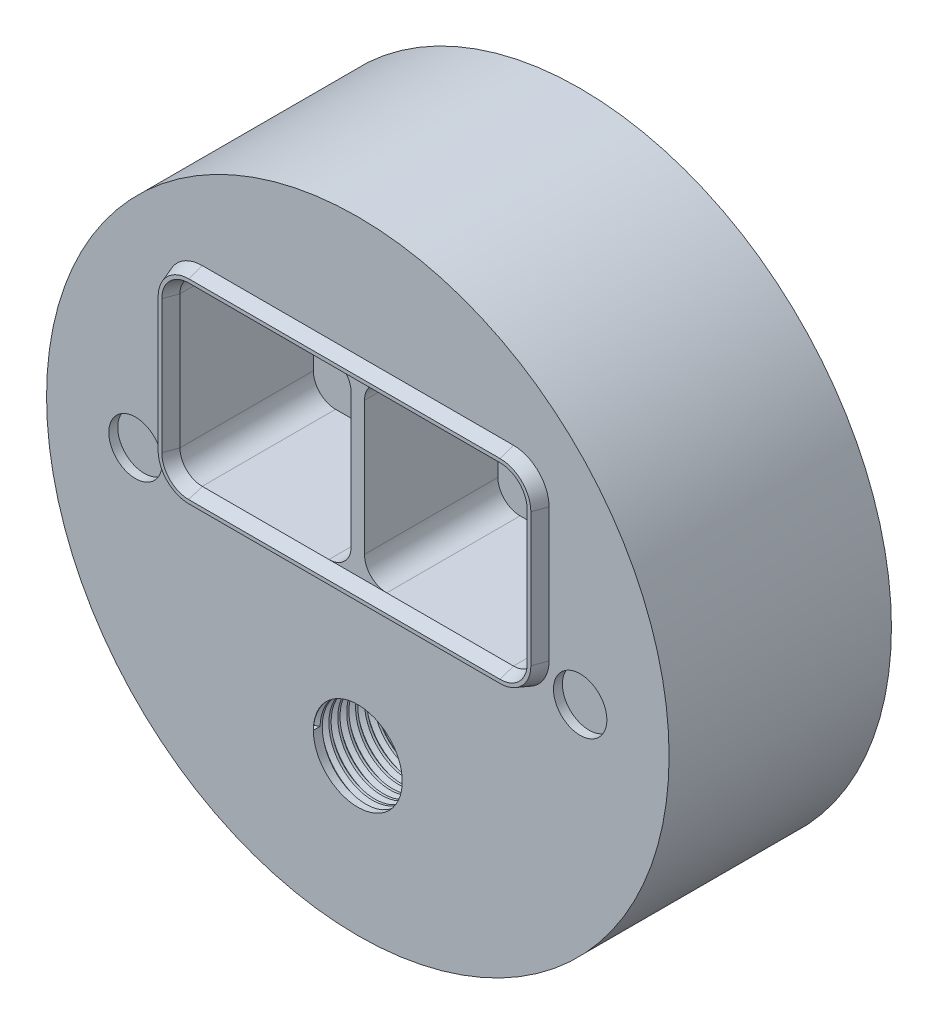
SolidWorks part; units mm, degrees
ref_plane "Front Plane" through (0, 0, 0) normal (0, 0, 1) x (1, 0, 0)
ref_plane "Top Plane" through (0, 0, 0) normal (0, 1, 0) x (1, 0, 0)
ref_plane "Right Plane" through (0, 0, 0) normal (1, 0, 0) x (0, 0, -1)
sketch "Sketch1" plane through (0, 0, 0) normal (0, 0, 1) x (1, 0, 0)
  line L0 (0, 0) -> (0, -35) construction
  line L1 (0, 0) -> (-25, 0) construction
  circle A0 centre (0, 0) radius 35
  circle A1 centre (0, -17.5) radius 5
  circle A2 centre (-25, 0) radius 3
  circle A3 centre (25, 0) radius 3
  dimension "D1" = 70
  dimension "D2" = 10
  dimension "D3" = 25
extrude "Boss-Extrude1" add sketch "Sketch1" along normal blind 25
thread "Thread1" pitch 1 start angle 0, offset 0, length 0, pitch 1, diameter 10
ref_plane "Plane1" through (-5, -17.5, 25) normal (0, -1, 0) x (-1, 0, 0)
sketch "Thread Profile1" plane through (-5, -17.5, 25) normal (0, -1, 0) x (-1, 0, 0)
  line L0 (0, 0) -> (0, 1) construction
  line L1 (0, 0) -> (0.5413, 0.3125)
  line L2 (0.5413, 0.3125) -> (0.5413, 0.4375)
  line L3 (0.5413, 0.4375) -> (0, 0.75)
  line L4 (0.5413, 0.375) -> (0, 0.375) construction
  line L11 (0, 0) -> (0, 0.75)
  point P2 (0, 0)
  dimension "Pitch" = 1
  dimension "Profile_Angle" = 60
  dimension "Profile_Land" = 0.125
  dimension "Profile_Height" = 0.5413
sketch "Sketch9" plane through (0, 0, 25) normal (0, 0, 1) x (1, 0, 0)
  circle A0 centre (-25, 0) radius 3
  circle A1 centre (25, 0) radius 3
extrude "Boss-Extrude2" add sketch "Sketch9" against normal up to surface (24 mm away) from offset 1 up to face at (22, 0, 0) offset against normal yes
sketch "Sketch10" plane through (0, 0, 25) normal (0, 0, 1) x (1, 0, 0)
  line L0 (0, 0) -> (0, 35) construction
  line L1 (-17.5, 20) -> (17.5, 20)
  line L2 (-20, 17.5) -> (-20, 2.5)
  line L3 (-17.5, 0) -> (17.5, 0)
  line L4 (20, 17.5) -> (20, 2.5)
  line L5 (0, 0) -> (0, 20) construction
  line L6 (-20, 10) -> (20, 10) construction
  circle A0 centre (0, 0) radius 35 construction
  arc A1 (-20, 2.5) -> (-17.5, 0) centre (-17.5, 2.5) ccw
  arc A2 (17.5, 0) -> (20, 2.5) centre (17.5, 2.5) ccw
  arc A3 (17.5, 20) -> (20, 17.5) centre (17.5, 17.5) cw
  arc A4 (-17.5, 20) -> (-20, 17.5) centre (-17.5, 17.5) ccw
  point P11 (-20, 0)
  point P16 (20, 20)
  point P19 (-20, 20)
  point P148 (0, 10)
  dimension "D4" = 2.5
  dimension "D1" = 10
  dimension "D2" = 20
  dimension "D3" = 40
extrude "Cut-Extrude1" cut sketch "Sketch10" against normal blind 15
sketch "Sketch11" plane through (0, 0, 10) normal (0, 0, 1) x (1, 0, 0)
  line L0 (0, 20) -> (0, 0) construction
  line L1 (17.5, 20) -> (-17.5, 20) construction
  line L2 (-17.5, 0) -> (17.5, 0) construction
  line L3 (0, 0) -> (0, 10) construction
  line L4 (0, 10) -> (20, 10) construction
  line L5 (20, 2.5) -> (20, 17.5) construction
  line L6 (-0.75, 17.5) -> (-0.75, 2.5)
  line L10 (0.75, 17.5) -> (0.75, 2.5)
  line L12 (-3.25, 20) -> (3.25, 20)
  line L13 (-3.25, 0) -> (3.25, 0)
  arc A1 (-3.25, 20) -> (-0.75, 17.5) centre (-3.25, 17.5) cw
  arc A2 (3.25, 20) -> (0.75, 17.5) centre (3.25, 17.5) ccw
  arc A3 (-3.25, 0) -> (-0.75, 2.5) centre (-3.25, 2.5) ccw
  arc A4 (3.25, 0) -> (0.75, 2.5) centre (3.25, 2.5) cw
  dimension "D1" = 2.5
  dimension ".15" = 1.5
extrude "Boss-Extrude3" add sketch "Sketch11" along normal up to surface (15 mm away) up to face at (0, 10, 25)
sketch "Sketch12" plane through (0, 0, 25) normal (0, 0, 1) x (1, 0, 0)
  line L0 (-3.25, 20) -> (-17.5, 20) construction
  line L1 (17.5, 20) -> (3.25, 20) construction
  line L2 (20, 2.5) -> (20, 17.5) construction
  line L3 (3.25, 0) -> (17.5, 0) construction
  line L4 (-17.5, 0) -> (-3.25, 0) construction
  line L5 (-20, 17.5) -> (-20, 2.5) construction
  line L6 (-3.25, 20) -> (-17.5, 20)
  line L7 (17.5, 20) -> (3.25, 20)
  line L8 (20, 2.5) -> (20, 17.5)
  line L9 (3.25, 0) -> (17.5, 0)
  line L10 (-17.5, 0) -> (-3.25, 0)
  line L11 (-20, 17.5) -> (-20, 2.5)
  line L12 (-3.25, 20) -> (3.25, 20)
  line L13 (-3.25, 0) -> (3.25, 0)
  line L14 (-3.25, -1.5) -> (3.25, -1.5)
  line L15 (3.25, -1.5) -> (17.5, -1.5)
  line L16 (21.5, 2.5) -> (21.5, 17.5)
  line L17 (17.5, 21.5) -> (3.25, 21.5)
  line L18 (-3.25, 21.5) -> (3.25, 21.5)
  line L19 (-3.25, 21.5) -> (-17.5, 21.5)
  line L20 (-21.5, 17.5) -> (-21.5, 2.5)
  line L21 (-17.5, -1.5) -> (-3.25, -1.5)
  arc A0 (20, 17.5) -> (17.5, 20) centre (17.5, 17.5) ccw construction
  arc A1 (17.5, 0) -> (20, 2.5) centre (17.5, 2.5) ccw construction
  arc A2 (-20, 2.5) -> (-17.5, 0) centre (-17.5, 2.5) ccw construction
  arc A3 (-17.5, 20) -> (-20, 17.5) centre (-17.5, 17.5) ccw construction
  arc A4 (20, 17.5) -> (17.5, 20) centre (17.5, 17.5) ccw
  arc A5 (17.5, 0) -> (20, 2.5) centre (17.5, 2.5) ccw
  arc A6 (-20, 2.5) -> (-17.5, 0) centre (-17.5, 2.5) ccw
  arc A7 (-17.5, 20) -> (-20, 17.5) centre (-17.5, 17.5) ccw
  arc A8 (17.5, -1.5) -> (21.5, 2.5) centre (17.5, 2.5) ccw
  arc A9 (21.5, 17.5) -> (17.5, 21.5) centre (17.5, 17.5) ccw
  arc A10 (-17.5, 21.5) -> (-21.5, 17.5) centre (-17.5, 17.5) ccw
  arc A11 (-21.5, 2.5) -> (-17.5, -1.5) centre (-17.5, 2.5) ccw
  dimension "D1" = 1.5
extrude "Boss-Extrude4" add sketch "Sketch12" along normal blind 1.5 draft 20
sketch "Sketch14" plane through (0, 0, 0) normal (0, 0, 1) x (1, 0, 0)
  line L0 (0, 0) -> (35, 0) construction
  line L1 (14.5611, 30) -> (14.0611, 30)
  line L2 (15.5611, 29) -> (15.5611, -29)
  line L3 (14.5611, -30) -> (14.0611, -30)
  line L4 (13.0611, 29) -> (13.0611, -29)
  line L5 (14.3111, -30) -> (14.3111, 30) construction
  line L6 (15.5611, 0) -> (13.0611, 0) construction
  circle A0 centre (0, 0) radius 35 construction
  arc A1 (15.5611, -29) -> (14.5611, -30) centre (14.5611, -29) cw
  arc A2 (14.0611, -30) -> (13.0611, -29) centre (14.0611, -29) cw
  arc A3 (14.5611, 30) -> (15.5611, 29) centre (14.5611, 29) cw
  arc A4 (14.0611, 30) -> (13.0611, 29) centre (14.0611, 29) ccw
  point P11 (15.5611, -30)
  point P16 (15.5611, 30)
  point P19 (13.0611, 30)
  point P1000 (14.3111, 0)
  dimension "D3" = 1
  dimension "D1" = 2.5
  dimension "D2" = 60
extrude "Cut-Extrude5" cut sketch "Sketch14" along normal blind 1 from surface at 0 starting at face at (35, 0, 0)
sketch "Sketch15" plane through (0, 0, 1) normal (0, 0, -1) x (-1, 0, 0)
  line L0 (-14.3111, -30) -> (-14.3111, 30) construction
  line L1 (-14.5611, -30) -> (-14.0611, -30) construction
  line L2 (-14.0611, 30) -> (-14.5611, 30) construction
  line L3 (-15.2253, 29.2498) -> (-15.2253, 28.8899)
  line L4 (-15.2253, 28.8899) -> (-14.3111, 28.2623)
  line L5 (-15.2253, 29.2498) -> (-14.3111, 28.6221)
  line L6 (-13.3968, 29.2498) -> (-13.3968, 28.8899)
  line L7 (-13.3968, 29.2498) -> (-14.3111, 28.6221)
  line L8 (-13.3968, 28.8899) -> (-14.3111, 28.2623)
  line L9 (-13.3968, 26.7498) -> (-13.3968, 26.3899)
  line L10 (-13.3968, 26.3899) -> (-14.3111, 25.7623)
  line L11 (-15.2253, 26.3899) -> (-14.3111, 25.7623)
  line L12 (-15.2253, 26.7498) -> (-15.2253, 26.3899)
  line L13 (-15.2253, 26.7498) -> (-14.3111, 26.1221)
  line L14 (-13.3968, 26.7498) -> (-14.3111, 26.1221)
  line L15 (-13.3968, 24.2498) -> (-13.3968, 23.8899)
  line L16 (-13.3968, 23.8899) -> (-14.3111, 23.2623)
  line L17 (-15.2253, 23.8899) -> (-14.3111, 23.2623)
  line L18 (-15.2253, 24.2498) -> (-15.2253, 23.8899)
  line L19 (-15.2253, 24.2498) -> (-14.3111, 23.6221)
  line L20 (-13.3968, 24.2498) -> (-14.3111, 23.6221)
  line L21 (-13.3968, 21.7498) -> (-13.3968, 21.3899)
  line L22 (-13.3968, 21.3899) -> (-14.3111, 20.7623)
  line L23 (-15.2253, 21.3899) -> (-14.3111, 20.7623)
  line L24 (-15.2253, 21.7498) -> (-15.2253, 21.3899)
  line L25 (-15.2253, 21.7498) -> (-14.3111, 21.1221)
  line L26 (-13.3968, 21.7498) -> (-14.3111, 21.1221)
  line L27 (-13.3968, 19.2498) -> (-13.3968, 18.8899)
  line L28 (-13.3968, 18.8899) -> (-14.3111, 18.2623)
  line L29 (-15.2253, 18.8899) -> (-14.3111, 18.2623)
  line L30 (-15.2253, 19.2498) -> (-15.2253, 18.8899)
  line L31 (-15.2253, 19.2498) -> (-14.3111, 18.6221)
  line L32 (-13.3968, 19.2498) -> (-14.3111, 18.6221)
  line L33 (-13.3968, 16.7498) -> (-13.3968, 16.3899)
  line L34 (-13.3968, 16.3899) -> (-14.3111, 15.7623)
  line L35 (-15.2253, 16.3899) -> (-14.3111, 15.7623)
  line L36 (-15.2253, 16.7498) -> (-15.2253, 16.3899)
  line L37 (-15.2253, 16.7498) -> (-14.3111, 16.1221)
  line L38 (-13.3968, 16.7498) -> (-14.3111, 16.1221)
  line L39 (-13.3968, 14.2498) -> (-13.3968, 13.8899)
  line L40 (-13.3968, 13.8899) -> (-14.3111, 13.2623)
  line L41 (-15.2253, 13.8899) -> (-14.3111, 13.2623)
  line L42 (-15.2253, 14.2498) -> (-15.2253, 13.8899)
  line L43 (-15.2253, 14.2498) -> (-14.3111, 13.6221)
  line L44 (-13.3968, 14.2498) -> (-14.3111, 13.6221)
  line L45 (-13.3968, 11.7498) -> (-13.3968, 11.3899)
  line L46 (-13.3968, 11.3899) -> (-14.3111, 10.7623)
  line L47 (-15.2253, 11.3899) -> (-14.3111, 10.7623)
  line L48 (-15.2253, 11.7498) -> (-15.2253, 11.3899)
  line L49 (-15.2253, 11.7498) -> (-14.3111, 11.1221)
  line L50 (-13.3968, 11.7498) -> (-14.3111, 11.1221)
  line L51 (-13.3968, 9.2498) -> (-13.3968, 8.8899)
  line L52 (-13.3968, 8.8899) -> (-14.3111, 8.2623)
  line L53 (-15.2253, 8.8899) -> (-14.3111, 8.2623)
  line L54 (-15.2253, 9.2498) -> (-15.2253, 8.8899)
  line L55 (-15.2253, 9.2498) -> (-14.3111, 8.6221)
  line L56 (-13.3968, 9.2498) -> (-14.3111, 8.6221)
  line L57 (-13.3968, 6.7498) -> (-13.3968, 6.3899)
  line L58 (-13.3968, 6.3899) -> (-14.3111, 5.7623)
  line L59 (-15.2253, 6.3899) -> (-14.3111, 5.7623)
  line L60 (-15.2253, 6.7498) -> (-15.2253, 6.3899)
  line L61 (-15.2253, 6.7498) -> (-14.3111, 6.1221)
  line L62 (-13.3968, 6.7498) -> (-14.3111, 6.1221)
  line L63 (-13.3968, 4.2498) -> (-13.3968, 3.8899)
  line L64 (-13.3968, 3.8899) -> (-14.3111, 3.2623)
  line L65 (-15.2253, 3.8899) -> (-14.3111, 3.2623)
  line L66 (-15.2253, 4.2498) -> (-15.2253, 3.8899)
  line L67 (-15.2253, 4.2498) -> (-14.3111, 3.6221)
  line L68 (-13.3968, 4.2498) -> (-14.3111, 3.6221)
  line L69 (-13.3968, 1.7498) -> (-13.3968, 1.3899)
  line L70 (-13.3968, 1.3899) -> (-14.3111, 0.7623)
  line L71 (-15.2253, 1.3899) -> (-14.3111, 0.7623)
  line L72 (-15.2253, 1.7498) -> (-15.2253, 1.3899)
  line L73 (-15.2253, 1.7498) -> (-14.3111, 1.1221)
  line L74 (-13.3968, 1.7498) -> (-14.3111, 1.1221)
  line L75 (-13.3968, -0.7502) -> (-13.3968, -1.1101)
  line L76 (-13.3968, -1.1101) -> (-14.3111, -1.7377)
  line L77 (-15.2253, -1.1101) -> (-14.3111, -1.7377)
  line L78 (-15.2253, -0.7502) -> (-15.2253, -1.1101)
  line L79 (-15.2253, -0.7502) -> (-14.3111, -1.3779)
  line L80 (-13.3968, -0.7502) -> (-14.3111, -1.3779)
  line L81 (-13.3968, -3.2502) -> (-13.3968, -3.6101)
  line L82 (-13.3968, -3.6101) -> (-14.3111, -4.2377)
  line L83 (-15.2253, -3.6101) -> (-14.3111, -4.2377)
  line L84 (-15.2253, -3.2502) -> (-15.2253, -3.6101)
  line L85 (-15.2253, -3.2502) -> (-14.3111, -3.8779)
  line L86 (-13.3968, -3.2502) -> (-14.3111, -3.8779)
  line L87 (-13.3968, -5.7502) -> (-13.3968, -6.1101)
  line L88 (-13.3968, -6.1101) -> (-14.3111, -6.7377)
  line L89 (-15.2253, -6.1101) -> (-14.3111, -6.7377)
  line L90 (-15.2253, -5.7502) -> (-15.2253, -6.1101)
  line L91 (-15.2253, -5.7502) -> (-14.3111, -6.3779)
  line L92 (-13.3968, -5.7502) -> (-14.3111, -6.3779)
  line L93 (-13.3968, -8.2502) -> (-13.3968, -8.6101)
  line L94 (-13.3968, -8.6101) -> (-14.3111, -9.2377)
  line L95 (-15.2253, -8.6101) -> (-14.3111, -9.2377)
  line L96 (-15.2253, -8.2502) -> (-15.2253, -8.6101)
  line L97 (-15.2253, -8.2502) -> (-14.3111, -8.8779)
  line L98 (-13.3968, -8.2502) -> (-14.3111, -8.8779)
  line L99 (-13.3968, -10.7502) -> (-13.3968, -11.1101)
  line L100 (-13.3968, -11.1101) -> (-14.3111, -11.7377)
  line L101 (-15.2253, -11.1101) -> (-14.3111, -11.7377)
  line L102 (-15.2253, -10.7502) -> (-15.2253, -11.1101)
  line L103 (-15.2253, -10.7502) -> (-14.3111, -11.3779)
  line L104 (-13.3968, -10.7502) -> (-14.3111, -11.3779)
  line L105 (-13.3968, -13.2502) -> (-13.3968, -13.6101)
  line L106 (-13.3968, -13.6101) -> (-14.3111, -14.2377)
  line L107 (-15.2253, -13.6101) -> (-14.3111, -14.2377)
  line L108 (-15.2253, -13.2502) -> (-15.2253, -13.6101)
  line L109 (-15.2253, -13.2502) -> (-14.3111, -13.8779)
  line L110 (-13.3968, -13.2502) -> (-14.3111, -13.8779)
  line L111 (-13.3968, -15.7502) -> (-13.3968, -16.1101)
  line L112 (-13.3968, -16.1101) -> (-14.3111, -16.7377)
  line L113 (-15.2253, -16.1101) -> (-14.3111, -16.7377)
  line L114 (-15.2253, -15.7502) -> (-15.2253, -16.1101)
  line L115 (-15.2253, -15.7502) -> (-14.3111, -16.3779)
  line L116 (-13.3968, -15.7502) -> (-14.3111, -16.3779)
  line L117 (-13.3968, -18.2502) -> (-13.3968, -18.6101)
  line L118 (-13.3968, -18.6101) -> (-14.3111, -19.2377)
  line L119 (-15.2253, -18.6101) -> (-14.3111, -19.2377)
  line L120 (-15.2253, -18.2502) -> (-15.2253, -18.6101)
  line L121 (-15.2253, -18.2502) -> (-14.3111, -18.8779)
  line L122 (-13.3968, -18.2502) -> (-14.3111, -18.8779)
  line L123 (-13.3968, -20.7502) -> (-13.3968, -21.1101)
  line L124 (-13.3968, -21.1101) -> (-14.3111, -21.7377)
  line L125 (-15.2253, -21.1101) -> (-14.3111, -21.7377)
  line L126 (-15.2253, -20.7502) -> (-15.2253, -21.1101)
  line L127 (-15.2253, -20.7502) -> (-14.3111, -21.3779)
  line L128 (-13.3968, -20.7502) -> (-14.3111, -21.3779)
  line L129 (-13.3968, -23.2502) -> (-13.3968, -23.6101)
  line L130 (-13.3968, -23.6101) -> (-14.3111, -24.2377)
  line L131 (-15.2253, -23.6101) -> (-14.3111, -24.2377)
  line L132 (-15.2253, -23.2502) -> (-15.2253, -23.6101)
  line L133 (-15.2253, -23.2502) -> (-14.3111, -23.8779)
  line L134 (-13.3968, -23.2502) -> (-14.3111, -23.8779)
  line L135 (-13.3968, -25.7502) -> (-13.3968, -26.1101)
  line L136 (-13.3968, -26.1101) -> (-14.3111, -26.7377)
  line L137 (-15.2253, -26.1101) -> (-14.3111, -26.7377)
  line L138 (-15.2253, -25.7502) -> (-15.2253, -26.1101)
  line L139 (-15.2253, -25.7502) -> (-14.3111, -26.3779)
  line L140 (-13.3968, -25.7502) -> (-14.3111, -26.3779)
  line L141 (-13.3968, -28.2502) -> (-13.3968, -28.6101)
  line L142 (-13.3968, -28.6101) -> (-14.3111, -29.2377)
  line L143 (-15.2253, -28.6101) -> (-14.3111, -29.2377)
  line L144 (-15.2253, -28.2502) -> (-15.2253, -28.6101)
  line L145 (-15.2253, -28.2502) -> (-14.3111, -28.8779)
  line L146 (-13.3968, -28.2502) -> (-14.3111, -28.8779)
  dimension "D1" = 24
extrude "Boss-Extrude5" add sketch "Sketch15" along normal blind 1 contours L6 L8 L4 L3 L5 L7 | L9 L10 L11 L12 L13 L14 | L15 L16 L17 L18 L19 L20 | L21 L22 L23 L24 L25 L26 | L27 L28 L29 L30 L31 L32 | L33 L34 L35 L36 L37 L38 | L39 L40 L41 L42 L43 L44 | L45 L46 L47 L48 L49 L50 | L51 L52 L53 L54 L55 L56 | L57 L58 L59 L60 L61 L62 | L63 L64 L65 L66 L67 L68 | L69 L70 L71 L72 L73 L74 | L75 L76 L77 L78 L79 L80 | L81 L82 L83 L84 L85 L86 | L87 L88 L89 L90 L91 L92 | L93 L94 L95 L96 L97 L98 | L99 L100 L101 L102 L103 L104 | L105 L106 L107 L108 L109 L110 | L111 L112 L113 L114 L115 L116 | L117 L118 L119 L120 L121 L122 | L123 L124 L125 L126 L127 L128 | L129 L130 L131 L132 L133 L134 | L135 L136 L137 L138 L139 L140 | L141 L142 L143 L144 L145 L146
sketch "Sketch16" plane through (0, 0, 0) normal (0, 0, -1) x (-1, 0, 0)
  line L0 (0, 0) -> (0, -35) construction
  line L1 (2.75, -32.5) -> (1.25, -32.5)
  line L2 (-2.75, -25) -> (-1.25, -25)
  line L3 (-3.75, -26) -> (-3.75, -31.5)
  line L4 (-2.75, -32.5) -> (-1.25, -32.5)
  line L6 (-2, -32.5) -> (-2, -25) construction
  line L7 (-3.75, -28.75) -> (-1.25, -28.75) construction
  line L8 (1.25, -26) -> (1.25, -32.5)
  line L9 (2.75, -25) -> (1.25, -25)
  line L10 (3.75, -26) -> (3.75, -31.5)
  line L11 (-1.25, -25) -> (1.25, -25)
  line L12 (-1.25, -26) -> (1.25, -26)
  line L13 (-1.25, -26) -> (-1.25, -32.5)
  circle A0 centre (0, 0) radius 35 construction
  arc A1 (-3.75, -31.5) -> (-2.75, -32.5) centre (-2.75, -31.5) ccw
  arc A2 (-2.75, -25) -> (-3.75, -26) centre (-2.75, -26) ccw
  arc A3 (3.75, -31.5) -> (2.75, -32.5) centre (2.75, -31.5) cw
  arc A4 (2.75, -25) -> (3.75, -26) centre (2.75, -26) cw
  point P12 (-3.75, -32.5)
  point P15 (-3.75, -25)
  point P402 (-2, -28.75)
  dimension "D5" = 1
  dimension "D1" = 2.5
  dimension "D3" = 7.5
  dimension "D4" = 2.5
extrude "Boss-Extrude6" add sketch "Sketch16" along normal blind 4
